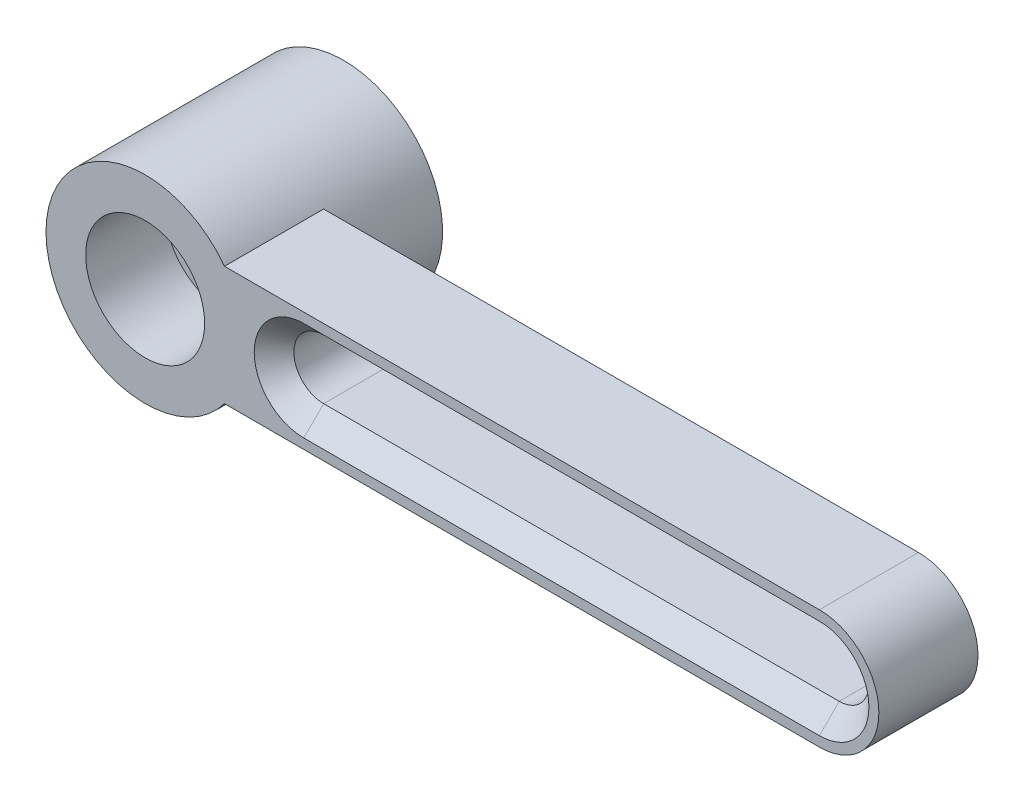
SolidWorks part; units mm, degrees
ref_plane "Спереди" through (0, 0, 0) normal (0, 0, 1) x (1, 0, 0)
ref_plane "Сверху" through (0, 0, 0) normal (0, 1, 0) x (1, 0, 0)
ref_plane "Справа" through (0, 0, 0) normal (1, 0, 0) x (0, 0, -1)
sketch "Эскиз1" plane through (0, 0, 0) normal (0, 0, 1) x (1, 0, 0)
  line L1 (-20, 3) -> (20, 3)
  line L2 (-20, 3) -> (-20, -3)
  line L3 (-20, -3) -> (20, -3)
  line L4 (20, 3) -> (20, -3)
  line L5 (-20, 3) -> (20, -3) construction
  line L6 (-20, -3) -> (20, 3) construction
  point P0 (0, 0)
  dimension "D1" = 40
  dimension "D2" = 6
extrude "Бобышка-Вытянуть1" add sketch "Эскиз1" along normal blind 5
sketch "Эскиз3" plane through (0, 0, 0) normal (0, 0, -1) x (-1, 0, 0)
  line L0 (20, 3) -> (20, -3) construction
  circle A0 centre (17, 0) radius 3
  dimension "D1" = 6
extrude "Бобышка-Вытянуть2" add sketch "Эскиз3" along normal blind 5
sketch "Эскиз4" plane through (0, 0, 0) normal (0, 0, -1) x (-1, 0, 0)
  line L0 (17, 3) -> (20, 3)
  line L1 (20, 3) -> (20, -3)
  line L2 (20, -3) -> (17, -3)
  arc A0 (17, -3) -> (20, 0) centre (17, 0) ccw
  arc A1 (17, 3) -> (20, 0) centre (17, 0) cw
extrude "Вырез-Вытянуть1" cut sketch "Эскиз4" against normal through all contours L0 A1 L1 | A0 L2 L1 region at (-19.3299, -2.3299, 0) region at (-19.3299, 2.3299, 0)
fillet "Скругление1" 2 edges at (20, 3, 2.5) (20, -3, 2.5) type full round first side face at (1.5, 3, 2.5) second side face at (1.5, -3, 2.5) middle face at (20, 0, 2.5)
sketch "Эскиз5" plane through (0, 0, 5) normal (0, 0, 1) x (1, 0, 0)
  line L0 (20, 0) -> (17, 0)
  line L2 (-9, 0) -> (-17, 0)
  line L3 (-9, 1.5) -> (17, 1.5)
  line L4 (-9, -1.5) -> (17, -1.5)
  arc A0 (-9, 1.5) -> (-9, -1.5) centre (-9, 0) ccw
  arc A1 (17, -1.5) -> (17, 1.5) centre (17, 0) ccw
  arc A2 (17, -3) -> (17, 3) centre (17, 0) ccw construction
  circle A3 centre (-17, 0) radius 1.5
  dimension "D1" = 3
  dimension "D2" = 3
  dimension "D5" = 3
  dimension "D3" = 3
  dimension "D4" = 26
extrude "Вырез-Вытянуть2" cut sketch "Эскиз5" against normal through all contours A1 L3 A0 L4 | A3 region at (4, 0, 5)
sketch "Эскиз6" plane through (0, 0, 5) normal (0, 0, 1) x (1, 0, 0)
  circle A0 centre (-17, 0) radius 2.5
  dimension "D1" = 5
extrude "Вырез-Вытянуть3" cut sketch "Эскиз6" against normal blind 3
chamfer "Фаска2" distance 1 angle 45 8 edges at (18.5, 0, 0) (4, 1.5, 0) (4, -1.5, 0) (-10.5, 0, 0) (-10.5, 0, 5) (4, -1.5, 5) (18.5, 0, 5) (4, 1.5, 5)
sketch "Эскиз7" plane through (0, 0, 5) normal (0, 0, 1) x (1, 0, 0)
  circle A0 centre (-17, 0) radius 4
  dimension "D1" = 8
extrude "Бобышка-Вытянуть3" add sketch "Эскиз7" against normal blind 10
sketch "Эскиз8" plane through (0, 0, 5) normal (0, 0, 1) x (1, 0, 0)
  circle A0 centre (-17, 0) radius 1.5
  dimension "D1" = 3
extrude "Вырез-Вытянуть4" cut sketch "Эскиз8" against normal through all
sketch "Эскиз9" plane through (0, 0, 5) normal (0, 0, 1) x (1, 0, 0)
  circle A0 centre (-17, 0) radius 3
  dimension "D1" = 6
extrude "Вырез-Вытянуть5" cut sketch "Эскиз9" against normal blind 2
sketch "Эскиз10" plane through (0, 0, 5) normal (0, 0, 1) x (1, 0, 0)
  circle A0 centre (-17, 0) radius 1.6
  dimension "D1" = 3.2
extrude "Вырез-Вытянуть6" cut sketch "Эскиз10" against normal through all
sketch "Эскиз11" plane through (0, 0, -5) normal (0, 0, -1) x (-1, 0, 0)
  circle A0 centre (17, 0) radius 5
  circle A1 centre (17, 0) radius 1.6
  dimension "D1" = 10
extrude "Бобышка-Вытянуть4" add sketch "Эскиз11" against normal blind 10
sketch "Эскиз12" plane through (0, 0, 5) normal (0, 0, 1) x (1, 0, 0)
  circle A0 centre (-17, 0) radius 3
  dimension "D1" = 6
extrude "Вырез-Вытянуть7" cut sketch "Эскиз12" against normal blind 4
